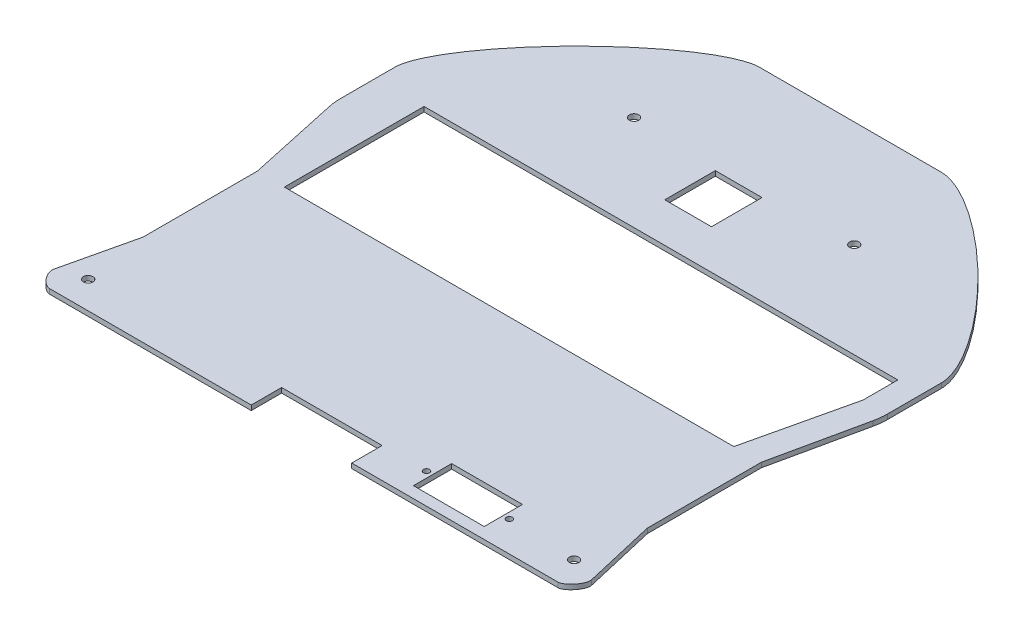
SolidWorks part; units mm, degrees
ref_plane "Front Plane" through (0, 0, 0) normal (0, 0, 1) x (1, 0, 0)
ref_plane "Top Plane" through (0, 0, 0) normal (0, 1, 0) x (1, 0, 0)
ref_plane "Right Plane" through (0, 0, 0) normal (1, 0, 0) x (0, 0, -1)
sketch "Sketch1" plane through (0, 0, 0) normal (0, 1, 0) x (1, 0, 0)
  line L0 (-90, 180) -> (-90, 0) construction
  line L1 (-180, 180) -> (0, 180)
  line L2 (-180, 180) -> (-180, 0)
  line L3 (-180, 0) -> (0, 0)
  line L4 (0, 180) -> (0, 0)
  line L5 (-180, 90) -> (0, 90) construction
  line L6 (-180, 30) -> (0, 30)
  line L7 (-130, 30) -> (-50, 30)
  line L8 (-130, 30) -> (-130, -30)
  line L9 (-130, -30) -> (-50, -30)
  line L10 (-50, 30) -> (-50, -30)
  line L11 (-130, 30) -> (-50, -30) construction
  line L12 (-130, -30) -> (-50, 30) construction
  dimension "D1" = 180
  dimension "D2" = 180
  dimension "D3" = 60
  dimension "D4" = 80
extrude "Boss-Extrude1" add sketch "Sketch1" along normal blind 1.6 contours L10 L3 L8 L9 | L2 L6 L4 L1 | L6 L10 L3 L4 | L8 L6 L2 L3 | L10 L6 L8 L3 region at (-90, 0, -105) region at (-155, 0, -15) region at (-25, 0, -15) region at (-90, 0, -15) region at (-90, 0, 15)
sketch "Sketch2" plane through (0, 1.6, 0) normal (0, 1, 0) x (1, 0, 0)
  line L0 (-180, 30) -> (0, 30)
  line L1 (-180, 180) -> (-180, 0) construction
  line L2 (0, 180) -> (0, 0) construction
  line L3 (-180, 180) -> (0, 180) construction
  line L4 (-90, 180) -> (-90, -30) construction
  line L5 (-130, -30) -> (-50, -30) construction
  dimension "D1" = 150
sketch "Sketch3" plane through (0, 1.6, 0) normal (0, 1, 0) x (1, 0, 0)
  line L0 (-180, 122) -> (0, 122)
  line L1 (-180, 180) -> (-180, 0) construction
  line L2 (0, 180) -> (0, 0) construction
  line L3 (-180, 30) -> (0, 30) construction
  dimension "D1" = 92
sketch "Sketch5" plane through (0, 1.6, 0) normal (0, 1, 0) x (1, 0, 0)
  line L0 (-114, 180) -> (-114, -30)
  line L1 (-180, 180) -> (0, 180) construction
  line L2 (-130, -30) -> (-50, -30) construction
  line L3 (-90, 180) -> (-90, -30) construction
  dimension "D1" = 24
fillet "Fillet1" radius 60 2 edges at (0, 0.8, -180) (-180, 0.8, -180) conic rho 0.2
sketch "Sketch6" plane through (0, 1.6, 0) normal (0, 1, 0) x (1, 0, 0)
  line L0 (-50, 0) -> (-130, 0)
  line L1 (-130, 0) -> (-130, -30)
  line L2 (-130, -30) -> (-50, -30)
  line L3 (-50, -30) -> (-50, 0)
  line L4 (-180, 0) -> (-173, 30.1113)
  line L5 (-173, 30.1113) -> (-173, 67.7113)
  line L6 (-173, 67.7113) -> (-180, 100)
  line L7 (-180, 120) -> (-180, 0) construction
  line L8 (-90, 180) -> (-90, -30) construction
  line L10 (-90, 180) -> (-90, 0) construction
  line L11 (0, 0) -> (-7, 30.1113)
  line L12 (-7, 30.1113) -> (-7, 67.7113)
  line L13 (-7, 67.7113) -> (0, 100)
  line M3 (0, 0) -> (0, 120)
  line M7 (-180, 120) -> (-180, 0)
  line M9 (-130, 0) -> (-130, -30)
  line M10 (-130, -30) -> (-50, -30)
  line M11 (-50, -30) -> (-50, 0)
  dimension "D1" = 37.6
  dimension "D2" = 83
  dimension "D3" = 100
extrude "Cut-Extrude1" cut sketch "Sketch6" against normal blind 10 contours L0 M11 M9 M10 | L5 L6 L4 M7 | L13 L12 L11 M3 region at (-90, 1.6, 15) region at (-177.0291, 1.6, -49.5379) region at (-2.9709, 1.6, -49.5379)
fillet "Fillet2" radius 5 2 edges at (-180, 0.8, 0) (0, 0.8, 0) conic rho 0.25
fillet "Fillet3" radius 20 2 edges at (-180, 0.8, -100) (0, 0.8, -100)
sketch "Sketch9" plane through (0, 1.6, 0) normal (0, 1, 0) x (1, 0, 0)
  line L0 (-173, 67.6) -> (-7, 67.6) construction
  line L1 (-173, 30.1113) -> (-173, 67.7113) construction
  line L2 (-7, 30.1113) -> (-7, 67.7113) construction
  line L3 (-180, 30) -> (0, 30) construction
  line L4 (-180, 113.6) -> (0, 113.6) construction
  line L5 (-180, 120) -> (-180, 102.143) construction
  line L6 (0, 120) -> (0, 102.143) construction
  line L7 (-16, 113.6) -> (-16, 67.6) construction
  line L8 (-90, 180) -> (-90, -30) construction
  line L9 (-164, 113.6) -> (-164, 67.6)
  line L10 (0, 102.143) -> (-16, 102.143) construction
  line L11 (-8, 102.143) -> (-8, 113.6)
  line L12 (-164, 113.6) -> (-8, 113.6)
  line L14 (-16, 67.6) -> (-164, 67.6)
  line L16 (-8, 102.143) -> (-16, 67.6)
  line L17 (-97.741, 143.2535) -> (-82.374, 143.2535)
  line L18 (-82.374, 143.2535) -> (-82.374, 126.6165)
  line L19 (-82.374, 126.6165) -> (-97.741, 126.6165)
  line L20 (-97.741, 126.6165) -> (-97.741, 143.2535)
  dimension "D1" = 37.6
  dimension "D2" = 46
  dimension "D3" = 74
  dimension "D4" = 74
extrude "Cut-Extrude3" cut sketch "Sketch9" against normal up to next
sketch "Sketch11" plane through (0, 1.6, 0) normal (0, 1, 0) x (1, 0, 0)
  line L0 (-173.7043, 0) -> (-6.2957, 0) construction
  line L2 (-114, 180) -> (-114, -30) construction
  line L3 (-180, 122) -> (0, 122) construction
  line L4 (-90, 180) -> (-90, 0) construction
  line L14 (-34.8, 15.8) -> (-57.1, 15.8) construction
  line L15 (-57.1, 15.8) -> (-57.1, 4.2) construction
  line L16 (-57.1, 4.2) -> (-34.8, 4.2) construction
  line L17 (-34.8, 4.2) -> (-34.8, 15.8) construction
  line L18 (-34.3, 16.3) -> (-57.6, 16.3)
  line L19 (-57.6, 16.3) -> (-57.6, 3.7)
  line L20 (-57.6, 3.7) -> (-34.3, 3.7)
  line L21 (-34.3, 3.7) -> (-34.3, 16.3)
  circle A0 centre (-170, 9) radius 1.55
  circle A1 centre (-126.25, 145) radius 1.55
  circle A2 centre (-10, 9) radius 1.55
  circle A3 centre (-53.75, 145) radius 1.55
  circle A4 centre (-32.3, 10) radius 1
  circle A5 centre (-59.6, 10) radius 1
  dimension "D1" = 3.1
  dimension "D2" = 9
  dimension "D4" = 3.1
  dimension "D5" = 12.25
  dimension "D6" = 23
  dimension "D7" = 2
  dimension "D8" = 2
  dimension "D3" = 80
  dimension "D9" = 0.5
extrude "Cut-Extrude5" cut sketch "Sketch11" against normal up to next
sketch "Sketch12" plane through (0, 1.6, 0) normal (0, 1, 0) x (1, 0, 0)
  line L1 (-173.7043, 0) -> (-6.2957, 0) construction
  line L12 (-107.3, 10) -> (-107.3, 0)
  line L13 (-107.3, 0) -> (-74.2129, 0)
  line L14 (-74.2129, 0) -> (-74.2129, 10)
  line L15 (-74.2129, 10) -> (-107.3, 10)
  circle A0 centre (-51.3, 10) radius 25 construction
  circle A1 centre (-51.3, 10) radius 56 construction
  arc A2 (-107.3, 10) -> (-106.3999, 0) centre (-51.3, 10) ccw construction
  arc A3 (-76.3, 10) -> (-74.2129, 0) centre (-51.3, 10) ccw construction
  dimension "D1" = 50
  dimension "D2" = 112
extrude "Cut-Extrude6" cut sketch "Sketch12" against normal up to next
